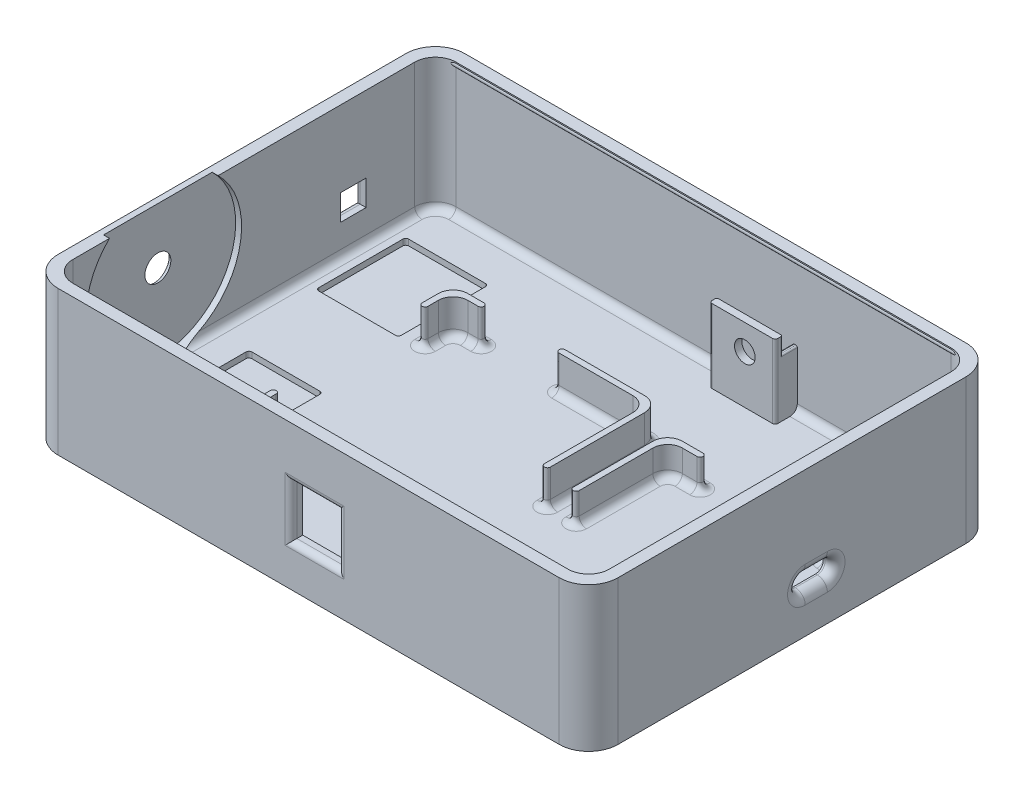
SolidWorks part; units mm, degrees
ref_plane "Front Plane" through (0, 0, 0) normal (0, 0, 1) x (1, 0, 0)
ref_plane "Top Plane" through (0, 0, 0) normal (0, 1, 0) x (1, 0, 0)
ref_plane "Right Plane" through (0, 0, 0) normal (1, 0, 0) x (0, 0, -1)
sketch "Sketch1" plane through (0, 0, 0) normal (0, 1, 0) x (1, 0, 0)
  line L0 (-95, -69) -> (-95, 69)
  line L1 (-91, -65) -> (91, -65)
  line L2 (-91, -65) -> (-91, 65)
  line L3 (-91, 65) -> (91, 65)
  line L4 (91, -65) -> (91, 65)
  line L5 (-91, -65) -> (91, 65) construction
  line L6 (-91, 65) -> (91, -65) construction
  line L7 (-95, 69) -> (95, 69)
  line L8 (95, -69) -> (95, 69)
  line L9 (-95, -69) -> (95, -69)
  point P0 (0, 0)
  dimension "D2" = 130
  dimension "D3" = 182
  dimension "D1" = 4
extrude "Box Sides" add sketch "Sketch1" along normal blind 45
fillet "Fillet1" radius 7 4 edges at (91, 22.5, 65) (91, 22.5, -65) (-91, 22.5, 65) (-91, 22.5, -65)
fillet "Fillet2" radius 10 4 edges at (95, 22.5, -69) (95, 22.5, 69) (-95, 22.5, 69) (-95, 22.5, -69)
sketch "Sketch2" plane through (0, 0, 0) normal (0, -1, 0) x (1, 0, 0)
  line L0 (-95, 59) -> (-95, -59)
  line L1 (-85, -69) -> (85, -69)
  line L2 (95, -59) -> (95, 59)
  line L3 (85, 69) -> (-85, 69)
  line L4 (-85, -69) -> (85, -69)
  line L5 (95, -59) -> (95, 59)
  line L6 (85, 69) -> (-85, 69)
  line L7 (-95, 59) -> (-95, -59)
  line L8 (-85, -69) -> (85, -69)
  line L9 (95, -59) -> (95, 59)
  line L10 (85, 69) -> (-85, 69)
  line L11 (-95, 59) -> (-95, -59)
  arc A0 (-85, 69) -> (-95, 59) centre (-85, 59) ccw
  arc A1 (-95, -59) -> (-85, -69) centre (-85, -59) ccw
  arc A2 (85, -69) -> (95, -59) centre (85, -59) ccw
  arc A3 (95, 59) -> (85, 69) centre (85, 59) ccw
  arc A4 (85, -69) -> (95, -59) centre (85, -59) ccw
  arc A5 (95, 59) -> (85, 69) centre (85, 59) ccw
  arc A6 (-85, 69) -> (-95, 59) centre (-85, 59) ccw
  arc A7 (-95, -59) -> (-85, -69) centre (-85, -59) ccw
  arc A8 (85, -69) -> (95, -59) centre (85, -59) ccw
  arc A9 (95, 59) -> (85, 69) centre (85, 59) ccw
  arc A10 (-85, 69) -> (-95, 59) centre (-85, 59) ccw
  arc A11 (-95, -59) -> (-85, -69) centre (-85, -59) ccw
  line M9 (-85, -69) -> (85, -69)
  arc M10 (85, -69) -> (95, -59) centre (85, -59) ccw
  line M11 (95, -59) -> (95, 59)
  arc M12 (95, 59) -> (85, 69) centre (85, 59) ccw
  line M13 (85, 69) -> (-85, 69)
  arc M14 (-85, 69) -> (-95, 59) centre (-85, 59) ccw
  line M15 (-95, 59) -> (-95, -59)
  arc M16 (-95, -59) -> (-85, -69) centre (-85, -59) ccw
  line M17 (-84, 65) -> (84, 65)
  arc M18 (84, 65) -> (91, 58) centre (84, 58) cw
  line M19 (91, 58) -> (91, -58)
  arc M20 (91, -58) -> (84, -65) centre (84, -58) cw
  line M21 (84, -65) -> (-84, -65)
  arc M22 (-84, -65) -> (-91, -58) centre (-84, -58) cw
  line M23 (-91, -58) -> (-91, 58)
  arc M24 (-91, 58) -> (-84, 65) centre (-84, 58) cw
  dimension "D1" = 0
extrude "Bottom" add sketch "Sketch2" along normal blind 4 contours M17 M24 M23 M22 M21 M20 M19 M18 | M16 M9 M10 M11 M12 M13 M14 M15 M24 M17 M18 M19 M20 M21 M22 M23 region at (-90.4106, 0, 64.4106) region at (0, 0, 0)
sketch "Sketch3" plane through (-95, 0, 0) normal (-1, 0, 0) x (0, 0, 1)
  line L1 (-41.5, 10.5) -> (-32.8, 10.5)
  line L2 (-41.5, 10.5) -> (-41.5, 19.2)
  line L3 (-41.5, 19.2) -> (-32.8, 19.2)
  line L4 (-59, 45) -> (-59, -4)
  line L5 (-59, -4) -> (59, -4)
  line L6 (59, -4) -> (59, 45)
  line L7 (59, 45) -> (-59, 45)
  line L8 (-59, 45) -> (-59, -4)
  line L9 (-59, -4) -> (59, -4)
  line L10 (59, -4) -> (59, 45)
  line L11 (59, 45) -> (-59, 45)
  line L12 (-32.8, 10.5) -> (-32.8, 19.2)
  line L13 (-41.5, 10.5) -> (-32.8, 19.2) construction
  line L14 (-41.5, 19.2) -> (-32.8, 10.5) construction
  line L19 (-58, 0) -> (58, 0) construction
  circle A8 centre (27.15, 26.1) radius 4.35
  point P2 (-37.15, 14.85)
  point P9 (27.15, 26.1)
  point P16 (0, 45)
  dimension "D4" = 8.7
  dimension "D2" = 37.15
  dimension "D3" = 27.15
  dimension "D5" = 8.7
  dimension "D6" = 14.5
  dimension "D7" = 26.1
  dimension "D1" = 0
extrude "Camera Holes" cut sketch "Sketch3" against normal up to next contours L2 L1 L12 L3 | A8
sketch "Sketch4" plane through (0, 0, 0) normal (0, 1, 0) x (1, 0, 0)
  line L0 (27.8, 25) -> (37.8, 25)
  line L1 (27.8, 25) -> (27.8, -5)
  line L3 (81, 27) -> (91, 27)
  line L4 (-84, -65) -> (84, -65)
  line L5 (91, -58) -> (91, 58)
  line L6 (84, 65) -> (-84, 65)
  line L7 (-91, 58) -> (-91, -58)
  line L8 (-84, -65) -> (84, -65)
  line L9 (91, -58) -> (91, 58)
  line L10 (84, 65) -> (-84, 65)
  line L11 (-91, 58) -> (-91, -58)
  line L12 (27.8, -35) -> (27.8, -65)
  line L13 (25.8, 27) -> (37.8, 27)
  line L14 (25.8, 27) -> (25.8, -5)
  line L15 (81, 25) -> (91, 25)
  line L16 (25.8, -35) -> (25.8, -65)
  line L17 (25.8, -65) -> (27.8, -65)
  line L18 (91, 27) -> (91, 25)
  arc A0 (37.8, 25) -> (37.8, 27) centre (37.8, 26) ccw
  arc A1 (27.8, -5) -> (25.8, -5) centre (26.8, -5) cw
  arc A2 (81, 27) -> (81, 25) centre (81, 26) ccw
  arc A4 (-91, -58) -> (-84, -65) centre (-84, -58) ccw
  arc A5 (84, -65) -> (91, -58) centre (84, -58) ccw
  arc A6 (91, 58) -> (84, 65) centre (84, 58) ccw
  arc A7 (-84, 65) -> (-91, 58) centre (-84, 58) ccw
  arc A8 (-91, -58) -> (-84, -65) centre (-84, -58) ccw
  arc A9 (84, -65) -> (91, -58) centre (84, -58) ccw
  arc A10 (91, 58) -> (84, 65) centre (84, 58) ccw
  arc A11 (-84, 65) -> (-91, 58) centre (-84, 58) ccw
  arc A12 (27.8, -35) -> (25.8, -35) centre (26.8, -35) ccw
  dimension "D8" = 2
  dimension "D2" = 63.2
  dimension "D3" = 10
  dimension "D4" = 10
  dimension "D5" = 90
  dimension "D6" = 30
  dimension "D7" = 30
  dimension "D1" = 0
extrude "Battery Cage" add sketch "Sketch4" along normal blind 10 contours A1 L1 L0 A0 L13 L14 | L3 A2 L15 L9 | L12 A12 L16 L8 | L3 L18 L15 A2 region at (27.4453, 0, -10) region at (85.605, 0, -26) region at (26.8, 0, 49.6065)
sketch "Sketch5" plane through (0, 0, 0) normal (0, 1, 0) x (1, 0, 0)
  line L0 (16, -65) -> (16, -35)
  line L1 (16, 30) -> (16, -5)
  line L3 (16, 30) -> (-14, 30)
  line L4 (-41.5, 30) -> (-50, 30)
  line L5 (-50, 30) -> (-50, 21.5)
  line L6 (-52, -65) -> (-52, -30)
  line L10 (91, -58) -> (91, 25)
  line L11 (91, 25) -> (81, 25)
  line L12 (81, 27) -> (91, 27)
  line L13 (91, 27) -> (91, 58)
  line L14 (84, 65) -> (-84, 65)
  line L15 (-91, 58) -> (-91, -58)
  line L16 (-84, -65) -> (25.8, -65)
  line L17 (25.8, -65) -> (25.8, -35)
  line L18 (27.8, -35) -> (27.8, -65)
  line L19 (27.8, -65) -> (84, -65)
  line L20 (91, -58) -> (91, 25)
  line L21 (91, 25) -> (81, 25)
  line L22 (81, 27) -> (91, 27)
  line L23 (91, 27) -> (91, 58)
  line L24 (84, 65) -> (-84, 65)
  line L25 (-91, 58) -> (-91, -58)
  line L26 (-84, -65) -> (25.8, -65)
  line L27 (25.8, -65) -> (25.8, -35)
  line L28 (27.8, -35) -> (27.8, -65)
  line L29 (27.8, -65) -> (84, -65)
  line L30 (-41.5, 32) -> (-52, 32)
  line L31 (-52, 32) -> (-52, 21.5)
  line L32 (18, 32) -> (18, -5)
  line L33 (18, 32) -> (-14, 32)
  line L34 (18, -65) -> (18, -35)
  line L35 (-50, -65) -> (-50, -30)
  line L36 (-52, -65) -> (-50, -65)
  line L37 (16, -65) -> (18, -65)
  arc A0 (-41.5, 30) -> (-41.5, 32) centre (-41.5, 31) ccw
  arc A1 (-50, 21.5) -> (-52, 21.5) centre (-51, 21.5) cw
  arc A2 (16, -5) -> (18, -5) centre (17, -5) ccw
  arc A3 (-14, 30) -> (-14, 32) centre (-14, 31) cw
  arc A5 (16, -35) -> (18, -35) centre (17, -35) cw
  arc A7 (-52, -30) -> (-50, -30) centre (-51, -30) cw
  arc A9 (81, 27) -> (81, 25) centre (81, 26) ccw
  arc A10 (91, 58) -> (84, 65) centre (84, 58) ccw
  arc A11 (-84, 65) -> (-91, 58) centre (-84, 58) ccw
  arc A12 (-91, -58) -> (-84, -65) centre (-84, -58) ccw
  arc A13 (27.8, -35) -> (25.8, -35) centre (26.8, -35) ccw
  arc A15 (84, -65) -> (91, -58) centre (84, -58) ccw
  arc A17 (81, 27) -> (81, 25) centre (81, 26) ccw
  arc A18 (91, 58) -> (84, 65) centre (84, 58) ccw
  arc A19 (-84, 65) -> (-91, 58) centre (-84, 58) ccw
  arc A20 (-91, -58) -> (-84, -65) centre (-84, -58) ccw
  arc A21 (27.8, -35) -> (25.8, -35) centre (26.8, -35) ccw
  arc A23 (84, -65) -> (91, -58) centre (84, -58) ccw
  dimension "D2" = 66
  dimension "D3" = 95
  dimension "D4" = 8.5
  dimension "D5" = 8.5
  dimension "D6" = 30
  dimension "D7" = 35
  dimension "D8" = 2
  dimension "D9" = 73
  dimension "D1" = 0
extrude "Pi Cage" add sketch "Sketch5" along normal blind 12 contours L1 A2 L32 L33 A3 L3 | L31 A1 L5 L4 A0 L30 | L6 A7 L35 L36 | L0 A5 L34 L37
fillet "Fillet3" radius 5 10 edges at (27.8, 5, -25) (91, 5, -25) (27.8, 5, 65) (25.8, 5, -27) (16, 6, 65) (-50, 6, 65) (18, 6, -32) (-50, 6, -30) (-52, 6, -32) (16, 6, -30)
sketch "Cam Mount Positions" plane through (0, 0, 0) normal (0, 1, 0) x (1, 0, 0)
  line L0 (-80.7, 46.7) -> (-80.7, 22.7)
  line L2 (-82.7, -10.65) -> (-56.7, -10.65) construction
  line L3 (-81.9655, 46.7) -> (-81.9655, 41.5) construction
  line L4 (-81.9655, 22.7) -> (-81.9655, 32.8) construction
  line L5 (-78.7, 46.7) -> (-78.7, 22.7)
  line L6 (-79.7, -13.65) -> (-79.7, -37.65)
  line L7 (-77.7, -13.65) -> (-77.7, -37.65)
  line L8 (-95, 59) -> (-95, -59) construction
  line L9 (-79.4387, -37.65) -> (-79.4387, -35.65) construction
  line L11 (-83.7, 49.7) -> (-57.7, 49.7) construction
  line L12 (-83.7, 49.7) -> (-83.7, 19.7) construction
  line L13 (-83.7, 19.7) -> (-57.7, 19.7) construction
  line L14 (-57.7, 49.7) -> (-57.7, 19.7) construction
  line L15 (-83.7, 49.7) -> (-57.7, 19.7) construction
  line L16 (-45, -65) -> (11, -65)
  line L17 (16, -60) -> (16, -35)
  line L18 (18, -35) -> (18, -65)
  line L19 (18, -65) -> (25.8, -65)
  line L20 (25.8, -65) -> (25.8, -35)
  line L21 (27.8, -35) -> (27.8, -60)
  line L22 (32.8, -65) -> (84, -65)
  line L23 (91, -58) -> (91, 20)
  line L24 (86, 25) -> (81, 25)
  line L25 (81, 27) -> (91, 27)
  line L26 (91, 27) -> (91, 58)
  line L27 (84, 65) -> (-84, 65)
  line L28 (-91, 58) -> (-91, -58)
  line L29 (-84, -65) -> (-52, -65)
  line L30 (-52, -65) -> (-52, -30)
  line L31 (-50, -30) -> (-50, -60)
  line L32 (-45, -65) -> (11, -65)
  line L33 (16, -60) -> (16, -35)
  line L34 (18, -35) -> (18, -65)
  line L35 (18, -65) -> (25.8, -65)
  line L36 (25.8, -65) -> (25.8, -35)
  line L37 (27.8, -35) -> (27.8, -60)
  line L38 (32.8, -65) -> (84, -65)
  line L39 (91, -58) -> (91, 20)
  line L40 (86, 25) -> (81, 25)
  line L41 (81, 27) -> (91, 27)
  line L42 (91, 27) -> (91, 58)
  line L43 (84, 65) -> (-84, 65)
  line L44 (-91, 58) -> (-91, -58)
  line L45 (-84, -65) -> (-52, -65)
  line L46 (-52, -65) -> (-52, -30)
  line L47 (-50, -30) -> (-50, -60)
  line L48 (-83.7, 19.7) -> (-57.7, 49.7) construction
  line L49 (-82.7, -10.65) -> (-82.7, -40.65) construction
  line L50 (-82.7, -40.65) -> (-56.7, -40.65) construction
  line L51 (-56.7, -10.65) -> (-56.7, -40.65) construction
  line L52 (-82.7, -10.65) -> (-56.7, -40.65) construction
  line L53 (-82.7, -40.65) -> (-56.7, -10.65) construction
  arc A1 (-80.7, 46.7) -> (-78.7, 46.7) centre (-79.7, 46.7) cw
  arc A2 (-80.7, 22.7) -> (-78.7, 22.7) centre (-79.7, 22.7) ccw
  arc A3 (-79.7, -13.65) -> (-77.7, -13.65) centre (-78.7, -13.65) cw
  arc A4 (-79.7, -37.65) -> (-77.7, -37.65) centre (-78.7, -37.65) ccw
  arc A12 (11, -65) -> (16, -60) centre (11, -60) ccw
  arc A13 (18, -35) -> (16, -35) centre (17, -35) ccw
  arc A14 (27.8, -35) -> (25.8, -35) centre (26.8, -35) ccw
  arc A15 (27.8, -60) -> (32.8, -65) centre (32.8, -60) ccw
  arc A16 (84, -65) -> (91, -58) centre (84, -58) ccw
  arc A17 (91, 20) -> (86, 25) centre (86, 20) ccw
  arc A18 (81, 27) -> (81, 25) centre (81, 26) ccw
  arc A19 (91, 58) -> (84, 65) centre (84, 58) ccw
  arc A20 (-84, 65) -> (-91, 58) centre (-84, 58) ccw
  arc A21 (-91, -58) -> (-84, -65) centre (-84, -58) ccw
  arc A22 (-50, -30) -> (-52, -30) centre (-51, -30) ccw
  arc A23 (-50, -60) -> (-45, -65) centre (-45, -60) ccw
  arc A24 (11, -65) -> (16, -60) centre (11, -60) ccw
  arc A25 (18, -35) -> (16, -35) centre (17, -35) ccw
  arc A26 (27.8, -35) -> (25.8, -35) centre (26.8, -35) ccw
  arc A27 (27.8, -60) -> (32.8, -65) centre (32.8, -60) ccw
  arc A28 (84, -65) -> (91, -58) centre (84, -58) ccw
  arc A29 (91, 20) -> (86, 25) centre (86, 20) ccw
  arc A30 (81, 27) -> (81, 25) centre (81, 26) ccw
  arc A31 (91, 58) -> (84, 65) centre (84, 58) ccw
  arc A32 (-84, 65) -> (-91, 58) centre (-84, 58) ccw
  arc A33 (-91, -58) -> (-84, -65) centre (-84, -58) ccw
  arc A34 (-50, -30) -> (-52, -30) centre (-51, -30) ccw
  arc A35 (-50, -60) -> (-45, -65) centre (-45, -60) ccw
  point P38 (-77.7, -25.65)
  point P60 (-70.7, 34.7)
  point P67 (-78.7, 34.7)
  point P68 (-69.7, -25.65)
  dimension "D2" = 24
  dimension "D3" = 14.3
  dimension "D4" = 5.2
  dimension "D5" = 2
  dimension "D6" = 15.3
  dimension "D7" = 2
  dimension "D8" = 30
  dimension "D9" = 26
  dimension "D10" = 7.3
  dimension "D11" = 26
  dimension "D12" = 30
  dimension "D13" = 8.3
  dimension "D1" = 0
fillet "Fillet4" radius 2.5 53 edges at (-48.5355, 0, 63.5355) (-50, 0, 45) (-51, 0, 29) (-52, 0, 47.5) (-68, 0, 65) (-88.9497, 0, 62.9497) (-91, 0, 0) (-88.9497, 0, -62.9497) (0, 0, -65) (88.9497, 0, -62.9497) (91, 0, -42.5) (86, 0, -27) (80, 0, -26) (83.5, 0, -25) (89.5355, 0, -23.5355) (91, 0, 19) (88.9497, 0, 62.9497) (58.4, 0, 65) (29.2645, 0, 63.5355) (27.8, 0, 47.5) (26.8, 0, 34) (25.8, 0, 50) (21.9, 0, 65) (18, 0, 50) (17, 0, 34) (16, 0, 47.5) (14.5355, 0, 63.5355) (-17, 0, 65) (38.8, 0, -26) (34.3, 0, -27) (27.2645, 0, -25.5355) (25.8, 0, -8.5) (26.8, 0, 6) (27.8, 0, -7.5) (29.2645, 0, -23.5355) (35.3, 0, -25) (17, 0, 6) (18, 0, -11) (16.5355, 0, -30.5355) (-0.5, 0, -32) (-15, 0, -31) (-1.5, 0, -30) (14.5355, 0, -28.5355) (16, 0, -10) (-40.5, 0, -31) (-44.25, 0, -32) (-50.5355, 0, -30.5355) (-52, 0, -24.25) (-51, 0, -20.5) (-50, 0, -23.25) (-48.5355, 0, -28.5355) (-43.25, 0, -30) (-95, 26.1, 31.5)
sketch "Sketch14" plane through (95, 0, 0) normal (1, 0, 0) x (0, 0, -1)
  line L0 (4.5, 11.2) -> (12, 11.2) construction
  line L1 (4.5, 13.8) -> (12, 13.8)
  line L2 (4.5, 8.6) -> (12, 8.6)
  line L3 (25.5, 45) -> (25.5, -4) construction
  line L4 (-59, 45) -> (-59, -4)
  line L5 (-59, -4) -> (59, -4)
  line L6 (59, -4) -> (59, 45)
  line L7 (59, 45) -> (-59, 45)
  line L8 (-59, 45) -> (-59, -4)
  line L9 (-59, -4) -> (59, -4)
  line L10 (59, -4) -> (59, 45)
  line L11 (59, 45) -> (-59, 45)
  line L12 (-65, 45) -> (-65, 2.5) construction
  arc A0 (4.5, 13.8) -> (4.5, 8.6) centre (4.5, 11.2) ccw
  arc A1 (12, 8.6) -> (12, 13.8) centre (12, 11.2) ccw
  point P6 (8.25, 11.2)
  dimension "D2" = 90.5
  dimension "D4" = 2.6
  dimension "D3" = 5.2
  dimension "D5" = 7.5
  dimension "D7" = 15.2
  dimension "D8" = 17.25
  dimension "D1" = 0
extrude "Power Button" cut sketch "Sketch14" against normal up to next contours L2 A1 L1 A0 region at (95, 11.2, -8.25)
fillet "Fillet5" radius 3.4 4 edges at (95, 11.2, -1.9) (95, 13.8, -8.25) (95, 11.2, -14.6) (95, 8.6, -8.25)
sketch "Sketch15" plane through (0, 0, 69) normal (0, 0, 1) x (1, 0, 0)
  line L0 (16, 2.5) -> (16, 12) construction
  line L1 (-6, 27.5) -> (10, 27.5)
  line L2 (-6, 27.5) -> (-6, 10)
  line L3 (-6, 10) -> (10, 10)
  line L4 (-85, 45) -> (-85, -4)
  line L5 (-85, -4) -> (85, -4)
  line L6 (85, -4) -> (85, 45)
  line L7 (85, 45) -> (-85, 45)
  line L8 (-85, 45) -> (-85, -4)
  line L9 (-85, -4) -> (85, -4)
  line L10 (85, -4) -> (85, 45)
  line L11 (85, 45) -> (-85, 45)
  line L12 (10, 27.5) -> (10, 10)
  line L13 (-6, 27.5) -> (10, 10) construction
  line L14 (-6, 10) -> (10, 27.5) construction
  point P2 (2, 18.75)
  dimension "D2" = 16
  dimension "D3" = 17.5
  dimension "D4" = 6
  dimension "D5" = 14
  dimension "D1" = 0
extrude "USBs" cut sketch "Sketch15" against normal up to next contours L2 L1 L12 L3
fillet "Fillet6" radius 2 4 edges at (2, 27.5, 69) (10, 18.75, 69) (-6, 18.75, 69) (2, 10, 69)
sketch "Sketch17" plane through (0, 0, 0) normal (0, 1, 0) x (1, 0, 0)
  line L0 (11, 60) -> (30.3, 60)
  line L1 (85, 69) -> (-85, 69) construction
  line L2 (11, 57.5) -> (30.3, 57.5)
  line L3 (20.65, 57.5) -> (20.65, 27.5) construction
  line L4 (11, 60) -> (11, 65)
  line L5 (-84, 65) -> (84, 65) construction
  line L6 (30.3, 60) -> (30.3, 65)
  line L7 (84, 65) -> (-84, 65) construction
  line L8 (11, 65) -> (9.5, 65)
  line L9 (9.5, 65) -> (9.5, 58.4)
  line L10 (10.4, 57.5) -> (11, 57.5)
  line L11 (30.3, 57.5) -> (30.9, 57.5)
  line L12 (31.8, 58.4) -> (31.8, 65)
  line L13 (31.8, 65) -> (30.3, 65)
  line L16 (-47.5, -30) -> (-47.5, -60)
  line L18 (-47.5, -30) -> (-47.5, -60)
  line L20 (-45, -62.5) -> (11, -62.5)
  line L22 (-45, -62.5) -> (11, -62.5)
  line L24 (13.5, -60) -> (13.5, -35)
  line L26 (13.5, -60) -> (13.5, -35)
  line L28 (20.5, -35) -> (20.5, -62.5)
  line L30 (20.5, -35) -> (20.5, -62.5)
  line L68 (20.5, -62.5) -> (23.3, -62.5)
  line L70 (20.5, -62.5) -> (23.3, -62.5)
  line L72 (23.3, -62.5) -> (23.3, -35)
  line L74 (23.3, -62.5) -> (23.3, -35)
  line L76 (30.3, -35) -> (30.3, -60)
  line L78 (30.3, -35) -> (30.3, -60)
  line L80 (32.8, -62.5) -> (84, -62.5)
  line L82 (32.8, -62.5) -> (84, -62.5)
  line L84 (88.5, -58) -> (88.5, 20)
  line L85 (88.5, -58) -> (88.5, 20)
  line L86 (86, 22.5) -> (81, 22.5)
  line L87 (86, 22.5) -> (81, 22.5)
  line L88 (81, 29.5) -> (88.5, 29.5)
  line L89 (81, 29.5) -> (88.5, 29.5)
  line L90 (88.5, 29.5) -> (88.5, 58)
  line L91 (88.5, 29.5) -> (88.5, 58)
  line L92 (84, 62.5) -> (-84, 62.5)
  line L93 (84, 62.5) -> (-84, 62.5)
  line L94 (-88.5, 58) -> (-88.5, -58)
  line L95 (-88.5, 58) -> (-88.5, -58)
  line L96 (-84, -62.5) -> (-54.5, -62.5)
  line L97 (-84, -62.5) -> (-54.5, -62.5)
  line L98 (-54.5, -62.5) -> (-54.5, -30)
  line L99 (-54.5, -62.5) -> (-54.5, -30)
  arc A2 (9.5, 58.4) -> (10.4, 57.5) centre (10.4, 58.4) ccw
  arc A3 (31.8, 58.4) -> (30.9, 57.5) centre (30.9, 58.4) cw
  arc A8 (-47.5, -30) -> (-54.5, -30) centre (-51, -30) ccw
  arc A10 (-47.5, -30) -> (-54.5, -30) centre (-51, -30) ccw
  arc A12 (20.5, -35) -> (13.5, -35) centre (17, -35) ccw
  arc A14 (20.5, -35) -> (13.5, -35) centre (17, -35) ccw
  arc A28 (30.3, -35) -> (23.3, -35) centre (26.8, -35) ccw
  arc A29 (30.3, -35) -> (23.3, -35) centre (26.8, -35) ccw
  arc A30 (84, -62.5) -> (88.5, -58) centre (84, -58) ccw
  arc A31 (84, -62.5) -> (88.5, -58) centre (84, -58) ccw
  arc A32 (81, 29.5) -> (81, 22.5) centre (81, 26) ccw
  arc A34 (81, 29.5) -> (81, 22.5) centre (81, 26) ccw
  arc A36 (88.5, 58) -> (84, 62.5) centre (84, 58) ccw
  arc A38 (88.5, 58) -> (84, 62.5) centre (84, 58) ccw
  arc A40 (-84, 62.5) -> (-88.5, 58) centre (-84, 58) ccw
  arc A42 (-84, 62.5) -> (-88.5, 58) centre (-84, 58) ccw
  arc A44 (-88.5, -58) -> (-84, -62.5) centre (-84, -58) ccw
  arc A46 (-88.5, -58) -> (-84, -62.5) centre (-84, -58) ccw
  arc A52 (-47.5, -60) -> (-45, -62.5) centre (-45, -60) ccw
  arc A53 (-47.5, -60) -> (-45, -62.5) centre (-45, -60) ccw
  arc A54 (11, -62.5) -> (13.5, -60) centre (11, -60) ccw
  arc A55 (11, -62.5) -> (13.5, -60) centre (11, -60) ccw
  arc A56 (30.3, -60) -> (32.8, -62.5) centre (32.8, -60) ccw
  arc A57 (30.3, -60) -> (32.8, -62.5) centre (32.8, -60) ccw
  arc A58 (88.5, 20) -> (86, 22.5) centre (86, 20) ccw
  arc A59 (88.5, 20) -> (86, 22.5) centre (86, 20) ccw
  dimension "D7" = 0.9
  dimension "D8" = 0.9
  dimension "D2" = 9
  dimension "D4" = 30
  dimension "D5" = 1.5
  dimension "D6" = 1.5
  dimension "D1" = 0
  dimension "D3" = 2.5
sketch "Sketch16" plane through (0, 0, -69) normal (0, 0, -1) x (-1, 0, 0)
  line L4 (85, 45) -> (-85, 45)
  line L5 (-85, 45) -> (-85, -4)
  line L6 (-85, -4) -> (85, -4)
  line L7 (85, -4) -> (85, 45)
  line L8 (85, 45) -> (-85, 45)
  line L9 (-85, 45) -> (-85, -4)
  line L10 (-85, -4) -> (85, -4)
  line L11 (85, -4) -> (85, 45)
  circle A0 centre (-21.5, 16.4) radius 3.5
  dimension "D2" = 7
  dimension "D3" = 63.5
  dimension "D4" = 20.4
  dimension "D1" = 0
fillet "Fillet9" radius 2 4 edges at (-95, 14.85, -41.5) (-95, 10.5, -37.15) (-95, 14.85, -32.8) (-95, 19.2, -37.15)
sketch "Sketch19" plane through (0, 0, 0) normal (0, 1, 0) x (1, 0, 0)
  line L1 (-86, 49.95) -> (-58, 49.95)
  line L2 (-86, 49.95) -> (-86, 19.45)
  line L3 (-86, 19.45) -> (-58, 19.45)
  line L4 (-58, 49.95) -> (-58, 19.45)
  line L5 (-86, 49.95) -> (-58, 19.45) construction
  line L6 (-86, 19.45) -> (-58, 49.95) construction
  line L7 (-79.46, -9.8) -> (-54.46, -9.8)
  line L8 (-79.46, -9.8) -> (-79.46, -40.3)
  line L9 (-79.46, -40.3) -> (-54.46, -40.3)
  line L10 (-54.46, -9.8) -> (-54.46, -40.3)
  line L11 (-79.46, -9.8) -> (-54.46, -40.3) construction
  line L12 (-79.46, -40.3) -> (-54.46, -9.8) construction
  line L14 (-91, 58) -> (-91, -58) construction
  line L15 (-86.5566, 34.7) -> (-86.5566, 32.8) construction
  line L16 (-85.5279, -58) -> (-85.5279, -25.05) construction
  line L21 (84, 62.5) -> (-84, 62.5)
  line L29 (84, 62.5) -> (-84, 62.5)
  line L70 (-88.5, 58) -> (-88.5, -58)
  line L78 (-88.5, 58) -> (-88.5, -58)
  line L86 (-84, -62.5) -> (-54.5, -62.5)
  line L90 (-84, -62.5) -> (-54.5, -62.5)
  line L94 (-54.5, -62.5) -> (-54.5, -30)
  line L98 (-54.5, -62.5) -> (-54.5, -30)
  line L102 (-47.5, -30) -> (-47.5, -60)
  line L104 (-47.5, -30) -> (-47.5, -60)
  line L106 (-45, -62.5) -> (11, -62.5)
  line L108 (-45, -62.5) -> (11, -62.5)
  line L110 (13.5, -60) -> (13.5, -35)
  line L112 (13.5, -60) -> (13.5, -35)
  line L114 (20.5, -35) -> (20.5, -62.5)
  line L116 (20.5, -35) -> (20.5, -62.5)
  line L118 (20.5, -62.5) -> (23.3, -62.5)
  line L119 (20.5, -62.5) -> (23.3, -62.5)
  line L120 (23.3, -62.5) -> (23.3, -35)
  line L121 (23.3, -62.5) -> (23.3, -35)
  line L122 (30.3, -35) -> (30.3, -60)
  line L123 (30.3, -35) -> (30.3, -60)
  line L124 (32.8, -62.5) -> (84, -62.5)
  line L125 (32.8, -62.5) -> (84, -62.5)
  line L126 (88.5, -58) -> (88.5, 20)
  line L127 (88.5, -58) -> (88.5, 20)
  line L128 (86, 22.5) -> (81, 22.5)
  line L129 (86, 22.5) -> (81, 22.5)
  line L130 (81, 29.5) -> (88.5, 29.5)
  line L131 (81, 29.5) -> (88.5, 29.5)
  line L132 (88.5, 29.5) -> (88.5, 58)
  line L133 (88.5, 29.5) -> (88.5, 58)
  arc A8 (-84, 62.5) -> (-88.5, 58) centre (-84, 58) ccw
  arc A13 (-84, 62.5) -> (-88.5, 58) centre (-84, 58) ccw
  arc A30 (-88.5, -58) -> (-84, -62.5) centre (-84, -58) ccw
  arc A38 (-88.5, -58) -> (-84, -62.5) centre (-84, -58) ccw
  arc A46 (-47.5, -30) -> (-54.5, -30) centre (-51, -30) ccw
  arc A47 (-47.5, -30) -> (-54.5, -30) centre (-51, -30) ccw
  arc A48 (20.5, -35) -> (13.5, -35) centre (17, -35) ccw
  arc A49 (20.5, -35) -> (13.5, -35) centre (17, -35) ccw
  arc A50 (30.3, -35) -> (23.3, -35) centre (26.8, -35) ccw
  arc A52 (30.3, -35) -> (23.3, -35) centre (26.8, -35) ccw
  arc A54 (84, -62.5) -> (88.5, -58) centre (84, -58) ccw
  arc A56 (84, -62.5) -> (88.5, -58) centre (84, -58) ccw
  arc A58 (81, 29.5) -> (81, 22.5) centre (81, 26) ccw
  arc A60 (81, 29.5) -> (81, 22.5) centre (81, 26) ccw
  arc A62 (88.5, 58) -> (84, 62.5) centre (84, 58) ccw
  arc A64 (88.5, 58) -> (84, 62.5) centre (84, 58) ccw
  arc A70 (-47.5, -60) -> (-45, -62.5) centre (-45, -60) ccw
  arc A71 (-47.5, -60) -> (-45, -62.5) centre (-45, -60) ccw
  arc A72 (11, -62.5) -> (13.5, -60) centre (11, -60) ccw
  arc A73 (11, -62.5) -> (13.5, -60) centre (11, -60) ccw
  arc A74 (30.3, -60) -> (32.8, -62.5) centre (32.8, -60) ccw
  arc A75 (30.3, -60) -> (32.8, -62.5) centre (32.8, -60) ccw
  arc A76 (88.5, 20) -> (86, 22.5) centre (86, 20) ccw
  arc A77 (88.5, 20) -> (86, 22.5) centre (86, 20) ccw
  point P0 (-72, 34.7)
  point P28 (-66.96, -25.05)
  dimension "D2" = 28
  dimension "D3" = 25
  dimension "D4" = 30.5
  dimension "D5" = 30.5
  dimension "D6" = 5
  dimension "D7" = 1.9
  dimension "D8" = 32.95
  dimension "D9" = 11.54
  dimension "D1" = 0
extrude "Cam Mounts" cut sketch "Sketch19" against normal blind 2 contours L2 L1 L4 L3 | L8 L7 L10 L9
extrude "Button Mount" add sketch "Sketch17" along normal blind 25 contours A3 L12 L6 L0 L4 L9 A2 L10 L2 L11 | L8 L9 L4 | L12 L13 L6 region at (20.65, 0, -59.0539) region at (10.25, 0, -63.75) region at (31.05, 0, -63.75)
extrude "Button Hole" cut sketch "Sketch16" against normal blind 20 contours A0
fillet "Fillet11" radius 3 1 edges at (18, 16.4, -69)
fillet "Fillet12" radius 1 8 edges at (-58, -1, -49.95) (-58, -1, -19.45) (-86, -1, -19.45) (-86, -1, -49.95) (-54.46, -1, 40.3) (-54.46, -1, 9.8) (-79.46, -1, 9.8) (-79.46, -1, 40.3)
sketch "Sketch20" plane through (0, 25, 0) normal (0, 1, 0) x (1, 0, 0)
  line L0 (11, 60) -> (9.5, 60)
  line L1 (9.5, 60) -> (31.8, 60)
  line L8 (31.8, 58.4) -> (31.8, 65)
  line L9 (31.8, 65) -> (30.3, 65)
  line L10 (30.3, 65) -> (30.3, 60)
  line L11 (30.3, 60) -> (11, 60)
  line L12 (11, 60) -> (11, 65)
  line L13 (11, 65) -> (9.5, 65)
  line L14 (9.5, 65) -> (9.5, 58.4)
  line L15 (10.4, 57.5) -> (30.9, 57.5)
  line L16 (31.8, 58.4) -> (31.8, 65)
  line L17 (31.8, 65) -> (30.3, 65)
  line L18 (30.3, 65) -> (30.3, 60)
  line L19 (30.3, 60) -> (11, 60)
  line L20 (11, 60) -> (11, 65)
  line L21 (11, 65) -> (9.5, 65)
  line L22 (9.5, 65) -> (9.5, 58.4)
  line L23 (10.4, 57.5) -> (30.9, 57.5)
  arc A2 (30.9, 57.5) -> (31.8, 58.4) centre (30.9, 58.4) ccw
  arc A3 (9.5, 58.4) -> (10.4, 57.5) centre (10.4, 58.4) ccw
  arc A4 (30.9, 57.5) -> (31.8, 58.4) centre (30.9, 58.4) ccw
  arc A5 (9.5, 58.4) -> (10.4, 57.5) centre (10.4, 58.4) ccw
  line M12 (31.8, 58.4) -> (31.8, 65)
  line M13 (31.8, 65) -> (30.3, 65)
  line M14 (30.3, 65) -> (30.3, 60)
  line M16 (11, 60) -> (11, 65)
  line M17 (11, 65) -> (9.5, 65)
  line M18 (9.5, 65) -> (9.5, 58.4)
  dimension "D1" = 0
extrude "Button Supports" cut sketch "Sketch20" against normal blind 5.5 contours L0 M16 M17 M18 | L1 M14 M12 M13 region at (10.25, 25, -62.5) region at (31.05, 25, -62.5)
fillet "Fillet13" radius 0.5 6 edges at (9.5, 22.25, -60) (31.8, 22.25, -60) (9.5, 19.5, -62.5) (11, 19.5, -62.5) (30.3, 19.5, -62.5) (31.8, 19.5, -62.5)
sketch "Sketch21" plane through (0, 0, 0) normal (1, 0, 0) x (0, 0, -1)
  line L0 (65, 44.58) -> (65, 43.42)
  line L1 (65, 45) -> (65, 2.5) construction
  line L3 (69, 45) -> (59, 45) construction
  line L4 (-65, 44.58) -> (-65, 43.42)
  line L5 (-59, 45) -> (-69, 45) construction
  line L8 (-65, 2.5) -> (-65, 45) construction
  arc A0 (65, 44.58) -> (65, 43.42) centre (65.8146, 44) ccw
  arc A1 (-65, 44.58) -> (-65, 43.42) centre (-65.8146, 44) cw
  dimension "D3" = 1
  dimension "D6" = 1
  dimension "D1" = 1.16
  dimension "D2" = 0.42
  dimension "D4" = 1.16
  dimension "D5" = 0.42
extrude "Lid Ridge" add sketch "Sketch21" along normal up to surface and the other way up to surface up to face at (91, 11.2, -8.25) other way up to face at (-91, 26.1, 22.8)
sketch "Sketch22" plane through (-91, 0, 0) normal (1, 0, 0) x (0, 0, -1)
  line L4 (-58, 45) -> (-58, 2.5)
  line L5 (-58, 2.5) -> (58, 2.5)
  line L6 (58, 2.5) -> (58, 45)
  line L7 (58, 45) -> (-58, 45)
  line L8 (-58, 45) -> (-58, 2.5)
  line L9 (-58, 2.5) -> (58, 2.5)
  line L10 (58, 2.5) -> (58, 45)
  line L11 (58, 45) -> (-58, 45)
  circle A0 centre (-27.15, 26.1) radius 26.4
  circle M5 centre (-27.15, 26.1) radius 4.35
  dimension "D2" = 52.8
  dimension "D1" = 0
extrude "Holder Insert" cut sketch "Sketch22" against normal blind 2.01 and the other way blind 14 contours L11 A0 L9 M5 | L11 A0 | L9 A0 region at (-91, 48.0398, 27.15) region at (-91, 44.3222, 27.15) region at (-91, 1.3747, 27.15)
equation "\"A\"= ( \"B\" - 20 ) / 4"
equation "\"B\"=108.204"
